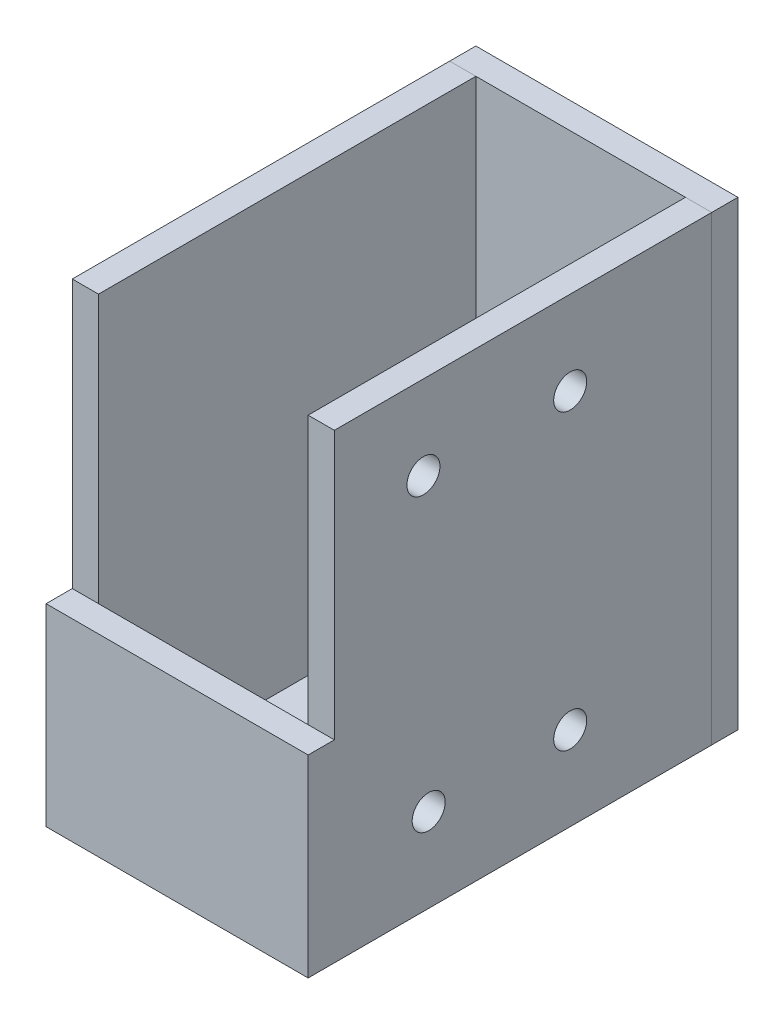
SolidWorks part; units mm, degrees
ref_plane "Front Plane" through (0, 0, 0) normal (0, 0, 1) x (1, 0, 0)
ref_plane "Top Plane" through (0, 0, 0) normal (0, 1, 0) x (1, 0, 0)
ref_plane "Right Plane" through (0, 0, 0) normal (1, 0, 0) x (0, 0, -1)
sketch "Sketch1" plane through (0, 0, 0) normal (0, 0, 1) x (1, 0, 0)
  line L0 (0, 0) -> (0, 55.88)
  line L1 (3.175, 55.88) -> (3.175, 3.175)
  line L2 (3.175, 3.175) -> (28.575, 3.175)
  line L3 (28.575, 3.175) -> (28.575, 55.88)
  line L4 (28.575, 55.88) -> (31.75, 55.88)
  line L5 (31.75, 55.88) -> (31.75, 0)
  line L6 (31.75, 0) -> (0, 0)
  line L7 (0, 55.88) -> (3.175, 55.88)
  dimension "D1" = 55.88
  dimension "D2" = 55.88
  dimension "D3" = 3.175
  dimension "D4" = 3.175
  dimension "D5" = 52.705
  dimension "D6" = 25.4
extrude "Boss-Extrude1" add sketch "Sketch1" along normal blind 45.72
ref_plane "Plane1" through (0, 0, 0) normal (0, 0, -1) x (-1, 0, 0)
sketch "Sketch2" plane through (0, 0, 0) normal (0, 0, -1) x (-1, 0, 0)
  line L0 (-31.75, 55.88) -> (-31.75, 0)
  line L1 (-31.75, 0) -> (0, 0)
  line L2 (0, 0) -> (0, 55.88)
  line L3 (0, 55.88) -> (-31.75, 55.88)
extrude "Boss-Extrude2" add sketch "Sketch2" along normal blind 3.175 separate body
ref_plane "Plane2" through (0, 0, 45.72) normal (0, 0, 1) x (1, 0, 0)
sketch "Sketch3" plane through (0, 0, 45.72) normal (0, 0, 1) x (1, 0, 0)
  line L0 (0, 55.88) -> (0, 0)
  line L1 (0, 0) -> (31.75, 0)
  line L2 (31.75, 0) -> (31.75, 55.88)
  line L3 (31.75, 55.88) -> (0, 55.88)
  line L4 (15.875, 55.88) -> (15.875, 0) construction
  line L5 (15.875, 55.88) -> (15.875, 40.4263) construction
  circle A0 centre (15.875, 40.4263) radius 3.7124
extrude "Boss-Extrude3" add sketch "Sketch3" along normal blind 3.175
ref_plane "Plane13" through (31.75, 0, 0) normal (1, 0, 0) x (0, 0, -1)
sketch "Sketch4" plane through (31.75, 0, 0) normal (1, 0, 0) x (0, 0, -1)
  line L0 (-48.895, 55.88) -> (3.175, 55.88) construction
  line L1 (3.175, 55.88) -> (-22.86, 55.88) construction
  line L2 (-22.86, 55.88) -> (-22.86, 0) construction
  line L3 (-48.895, 0) -> (0, 0) construction
  line L5 (-45.72, 55) -> (-45.72, -55) construction
  line L6 (0, -17.4625) -> (0, 17.4625) construction
  line L11 (0, 55.88) -> (-22.86, 55.88) construction
  line L12 (-11.43, 55.88) -> (-11.43, 0) construction
  line L13 (-22.86, 55.88) -> (-45.72, 55.88) construction
  line L14 (-45.72, 55.88) -> (-34.29, 55.88) construction
  line L15 (-34.29, 55.88) -> (-34.29, 0) construction
  line L16 (-45.72, 45.72) -> (0, 45.72) construction
  line L17 (0, 45.72) -> (0, 10.16) construction
  line L18 (0, 10.16) -> (-45.72, 10.16) construction
  line L19 (-11.43, 55.88) -> (0, 55.88)
  line L20 (0, 55.88) -> (0, 45.72)
  line L21 (0, 10.16) -> (0, 0)
  line L22 (-34.925, 45.72) -> (-17.145, 45.72) construction
  line L23 (-17.145, 45.72) -> (-17.145, 10.16) construction
  line L24 (-48.895, 0) -> (-48.895, 55.88) construction
  circle A1 centre (-17.145, 45.72) radius 2
  circle A2 centre (-34.29, 10.16) radius 2
  circle A3 centre (-17.145, 10.16) radius 2
  circle A4 centre (-34.925, 45.72) radius 2
  point P23 (-34.925, 45.72)
  point P28 (-17.145, 45.72)
  point P29 (-17.145, 10.16)
  point P30 (-34.29, 10.16)
  dimension "D6" = 17.78
  dimension "D1" = 11.43
  dimension "D2" = 10.16
  dimension "D3" = 10.16
  dimension "D4" = 11.43
  dimension "D5" = 11.43
  dimension "D7" = 13.97
extrude "Cut-Extrude1" cut sketch "Sketch4" against normal blind 3.175 contours A1 | A3 | A2 | A4 region at (31.75, 45.72, 17.145) region at (31.75, 10.16, 34.29) region at (31.75, 10.16, 17.145)
sketch "Sketch5" plane through (0, 0, 48.895) normal (0, 0, 1) x (1, 0, 0)
  line L0 (31.75, -26.8922) -> (31.75, 26.8923) construction
  line L1 (0, 55.88) -> (31.75, 55.88)
  line L2 (0, 55.88) -> (0, 23.4009)
  line L3 (0, 23.4009) -> (31.75, 23.4009)
  line L4 (31.75, 55.88) -> (31.75, 23.4009)
extrude "Cut-Extrude2" cut sketch "Sketch5" against normal blind 3.175
